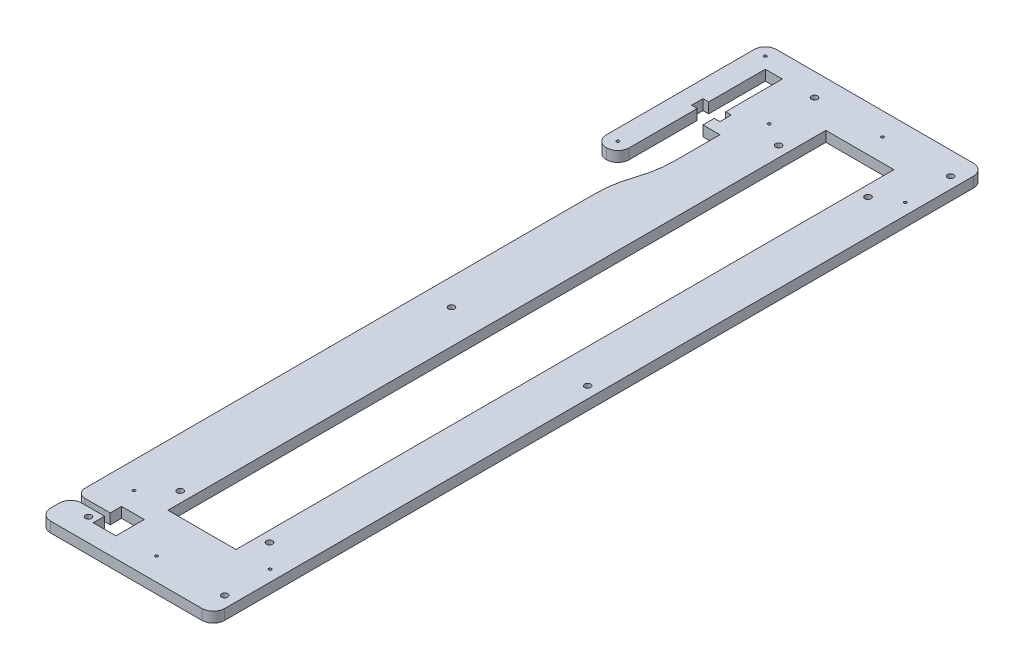
SolidWorks part; units mm, degrees
material "Balsa"
ref_plane "Front Plane" through (0, 0, 0) normal (0, 0, 1) x (1, 0, 0)
ref_plane "Top Plane" through (0, 0, 0) normal (0, 1, 0) x (1, 0, 0)
ref_plane "Right Plane" through (0, 0, 0) normal (1, 0, 0) x (0, 0, -1)
sketch "Sketch1" plane through (0, 0, 0) normal (0, 1, 0) x (1, 0, 0)
  line L1 (0, 0) -> (-88.9, 0)
  line L2 (0, 0) -> (0, -431.8)
  line L3 (0, -431.8) -> (-88.9, -431.8)
  line L4 (-88.9, 0) -> (-88.9, -431.8)
  dimension "D1" = 88.9
  dimension "D2" = 431.8
extrude "Boss-Extrude1" add sketch "Sketch1" along normal blind 5.8
hole_wizard "M3 Clearance Hole1" positions "Sketch6" profile "Sketch5" hole size "M3" standard "Ansi Metric" end condition through all
sketch "Sketch6" plane through (0, 5.8, 0) normal (0, 1, 0) x (-1, 0, 0)
  line L0 (44.45, 0) -> (44.45, 431.8) construction
  line L1 (0, 0) -> (88.9, 0) construction
  line L2 (88.9, 431.8) -> (0, 431.8) construction
  line L4 (44.45, 215.9) -> (88.9, 215.9) construction
  line L7 (44.45, 215.9) -> (0, 215.9) construction
  line L10 (82.55, 12.7) -> (82.55, 215.9) construction
  line L12 (6.35, 12.7) -> (6.35, 215.9) construction
  line L13 (82.55, 419.1) -> (6.35, 419.1) construction
  line L14 (82.55, 419.1) -> (82.55, 215.9) construction
  line L16 (6.35, 419.1) -> (6.35, 215.9) construction
  line L17 (0, 431.8) -> (0, 0) construction
  line L18 (88.9, 0) -> (88.9, 431.8) construction
  point P0 (82.55, 12.7)
  point P17 (6.35, 12.7)
  point P19 (6.35, 419.1)
  point P20 (82.55, 419.1)
  point P21 (82.55, 215.9)
  point P25 (6.35, 215.9)
  dimension "D1" = 76.2
  dimension "D2" = 12.7
  dimension "D3" = 406.4
sketch "Sketch5" plane through (-82.55, 5.8, 12.7) normal (1, 0, 0) x (0, 0, 1)
  line L0 (0, 0) -> (0, 5.8)
  line L1 (0, 5.8) -> (1.7, 5.8)
  line L2 (1.7, 5.8) -> (1.7, 0)
  line L5 (1.7, 0) -> (0, 0)
  line L11 (0, -6.35) -> (0, 107.95) construction
  dimension "Thru Hole Dia." = 3.4
  dimension "Thru Hole Depth" = 5.8
sketch "Sketch2" plane through (0, 5.8, 0) normal (0, 1, 0) x (1, 0, 0)
  line L1 (-44.45, -393.7) -> (-44.45, -25.4) construction
  line L2 (0, 0) -> (-88.9, 0) construction
  line L3 (-44.45, -209.55) -> (-88.9, -209.55) construction
  line L5 (-63.5, -25.4) -> (-25.4, -25.4)
  line L6 (-44.45, -209.55) -> (0, -209.55) construction
  line L8 (-63.5, -25.4) -> (-63.5, -393.7)
  line L9 (-63.5, -393.7) -> (-25.4, -393.7)
  line L10 (-25.4, -25.4) -> (-25.4, -393.7)
  line L11 (-88.9, 0) -> (-88.9, -431.8) construction
  line L12 (0, -431.8) -> (0, 0) construction
  dimension "D2" = 368.3
  dimension "D1" = 38.1
  dimension "D3" = 25.4
sketch "Sketch3" plane through (0, 5.8, 0) normal (0, 1, 0) x (-1, 0, 0)
  line L0 (88.9, 431.8) -> (0, 431.8) construction
  line L1 (88.9, 0) -> (97.4, 0)
  line L2 (88.9, 0) -> (88.9, 431.8)
  line L3 (88.9, 431.8) -> (97.4, 431.8)
  line L4 (97.4, 0) -> (97.4, 431.8)
  dimension "D1" = 8.5
extrude "Cut-Extrude1" cut sketch "Sketch2" against normal through all
sketch "Sketch7" plane through (0, 5.8, 0) normal (0, 1, 0) x (1, 0, 0)
  line L0 (-82.55, -12.7) -> (-6.35, -12.7) construction
  line L1 (-82.55, -215.9) -> (-6.35, -215.9) construction
  line L2 (-44.45, -25.4) -> (-44.45, -393.7) construction
  line L3 (-25.4, -25.4) -> (-63.5, -25.4) construction
  line L4 (-63.5, -393.7) -> (-25.4, -393.7) construction
  line L5 (-82.55, -12.7) -> (-82.55, -215.9) construction
  line L6 (-6.35, -12.7) -> (-6.35, -215.9) construction
  line L7 (-82.55, -38.1) -> (-6.35, -38.1) construction
  line L8 (-82.55, -393.7) -> (-6.35, -393.7) construction
  line L9 (-44.45, -419.1) -> (-44.45, -393.7) construction
  line L10 (-44.45, -419.1) -> (-44.45, -431.8) construction
  line L11 (-88.9, -431.8) -> (0, -431.8) construction
  line L12 (-82.55, -393.7) -> (-82.55, -419.1) construction
  circle A0 centre (-44.45, -12.7) radius 0.7937
  circle A1 centre (-82.55, -38.1) radius 0.7937
  circle A2 centre (-6.35, -38.1) radius 0.7938
  circle A3 centre (-6.35, -393.7) radius 0.7938
  circle A4 centre (-82.55, -393.7) radius 0.7937
  circle A5 centre (-44.45, -419.1) radius 0.7938
  dimension "D1" = 1.5875
  dimension "D2" = 25.4
  dimension "D3" = 25.4
  dimension "D4" = 355.6
extrude "Boss-Extrude2" add sketch "Sketch3" against normal through all
extrude "Cut-Extrude2" cut sketch "Sketch7" against normal through all
sketch "Sketch9" plane through (0, 5.8, 0) normal (0, 1, 0) x (1, 0, 0)
  line L1 (-97.4, 0) -> (-122.8, 0)
  line L2 (-97.4, 0) -> (-97.4, -95.25)
  line L3 (-97.4, -95.25) -> (-122.8, -95.25)
  line L4 (-122.8, 0) -> (-122.8, -95.25)
  dimension "D1" = 25.4
  dimension "D2" = 95.25
extrude "Boss-Extrude3" add sketch "Sketch9" against normal through all
sketch "Sketch8" plane through (0, 5.8, 0) normal (0, 1, 0) x (1, 0, 0)
  line L0 (-110.1, -44.45) -> (-113.275, -44.45)
  line L1 (-110.1, -12.7) -> (-100.575, -12.7)
  line L2 (-110.1, -12.7) -> (-110.1, -44.45)
  line L3 (-100.575, -44.45) -> (-97.4, -44.45)
  line L4 (-100.575, -12.7) -> (-100.575, -44.45)
  line L5 (-113.275, -50.8) -> (-110.1, -50.8)
  line L6 (-100.575, -50.8) -> (-100.575, -57.15)
  line L7 (-97.4, -44.45) -> (-97.4, -50.8)
  line L8 (-100.575, -57.15) -> (-91.05, -57.15)
  line L9 (-113.275, -44.45) -> (-113.275, -50.8)
  line L10 (-149.7875, -82.55) -> (-38.6625, -120.65) construction
  line L11 (-91.05, -57.15) -> (-91.05, -82.55)
  line L12 (-122.8, -95.25) -> (-97.4, -95.25) construction
  line L13 (-100.575, -50.8) -> (-97.4, -50.8)
  line L14 (0, 0) -> (-122.8, 0) construction
  line L15 (-110.1, -95.25) -> (-110.1, -50.8)
  line L16 (-122.8, 0) -> (-122.8, -95.25) construction
  line L17 (-91.05, -82.55) -> (-91.05, -120.65) construction
  line L18 (-91.05, -120.65) -> (-97.4, -120.65) construction
  line L19 (-97.4, -95.25) -> (-97.4, -431.8) construction
  line L20 (-97.4, -120.65) -> (-97.4, -95.25)
  line L21 (-97.4, -95.25) -> (-110.1, -95.25)
  arc A0 (-91.05, -82.55) -> (-94.225, -101.6) centre (-149.7875, -82.55) cw
  arc A1 (-94.225, -101.6) -> (-97.4, -120.65) centre (-38.6625, -120.65) ccw
  dimension "D1" = 9.525
  dimension "D2" = 31.75
  dimension "D3" = 12.7
  dimension "D4" = 15.875
  dimension "D5" = 6.35
  dimension "D6" = 12.7
  dimension "D7" = 9.525
  dimension "D8" = 6.35
  dimension "D9" = 25.4
  dimension "D11" = 25.4
extrude "Cut-Extrude3" cut sketch "Sketch8" against normal through all
sketch "Sketch10" plane through (0, 5.8, 0) normal (0, 1, 0) x (1, 0, 0)
  line L1 (-116.45, 0) -> (-116.45, -95.25) construction
  line L2 (0, 0) -> (-122.8, 0) construction
  line L3 (-122.8, -95.25) -> (-110.1, -95.25) construction
  line L4 (-122.8, 0) -> (-122.8, -95.25) construction
  circle A0 centre (-116.45, -88.9) radius 0.7937
  circle A1 centre (-116.45, -6.35) radius 0.7937
  dimension "D1" = 6.35
  dimension "D2" = 6.35
  dimension "D3" = 1.5875
  dimension "D4" = 6.35
extrude "Cut-Extrude4" cut sketch "Sketch10" against normal through all
sketch "Sketch11" plane through (0, 5.8, 0) normal (0, 1, 0) x (1, 0, 0)
  line L0 (-97.4, -120.65) -> (-97.4, -431.8) construction
  line L1 (-97.4, -414.3375) -> (-78.35, -414.3375)
  line L2 (-97.4, -414.3375) -> (-97.4, -411.1625)
  line L3 (-97.4, -411.1625) -> (-78.35, -411.1625)
  line L4 (-78.35, -411.1625) -> (-78.35, -404.8125)
  line L5 (-78.35, -404.8125) -> (-65.65, -404.8125)
  line L6 (-65.65, -420.6875) -> (-65.65, -404.8125)
  line L7 (-65.65, -420.6875) -> (-78.35, -420.6875)
  line L8 (-78.35, -420.6875) -> (-78.35, -414.3375)
  line L9 (-97.4, -412.75) -> (-63.5, -412.75) construction
  line L10 (-97.4, -431.8) -> (0, -431.8) construction
  dimension "D1" = 15.875
  dimension "D2" = 12.7
  dimension "D3" = 3.175
  dimension "D4" = 19.05
  dimension "D5" = 19.05
extrude "Cut-Extrude5" cut sketch "Sketch11" against normal through all
fillet "Fillet1" radius 5 1 edges at (-97.4, 2.9, 411.1625)
fillet "Fillet2" radius 6.35 7 edges at (0, 2.9, 431.8) (-97.4, 2.9, 414.3375) (-97.4, 2.9, 431.8) (-122.8, 2.9, 95.25) (0, 2.9, 0) (-122.8, 2.9, 0) (-110.1, 2.9, 95.25)
sketch "Sketch12" plane through (0, 0, 0) normal (0, -1, 0) x (1, 0, 0)
  line L0 (-69.45, 431.8) -> (-69.45, 380.9) construction
  line L1 (-91.05, 431.8) -> (-6.35, 431.8) construction
  line L2 (-44.45, 393.7) -> (-44.45, 380.9) construction
  line L3 (-63.5, 393.7) -> (-25.4, 393.7) construction
  line L4 (-69.45, 0) -> (-69.45, 45.9) construction
  line L5 (-6.35, 0) -> (-116.45, 0) construction
  line L6 (-44.45, 25.4) -> (-44.45, 45.9) construction
  line L7 (-25.4, 25.4) -> (-63.5, 25.4) construction
  line L8 (-44.45, 45.9) -> (-69.45, 45.9) construction
  line L9 (-44.45, 380.9) -> (-69.45, 380.9) construction
  circle A0 centre (-69.45, 380.9) radius 1.7272
  circle A1 centre (-19.45, 380.9) radius 1.7272
  circle A2 centre (-69.45, 45.9) radius 1.7272
  circle A3 centre (-19.45, 45.9) radius 1.7272
  dimension "D2" = 3.4544
  dimension "D1" = 50.9
  dimension "D3" = 25
  dimension "D4" = 45.9
extrude "Cut-Extrude6" cut sketch "Sketch12" against normal through all
